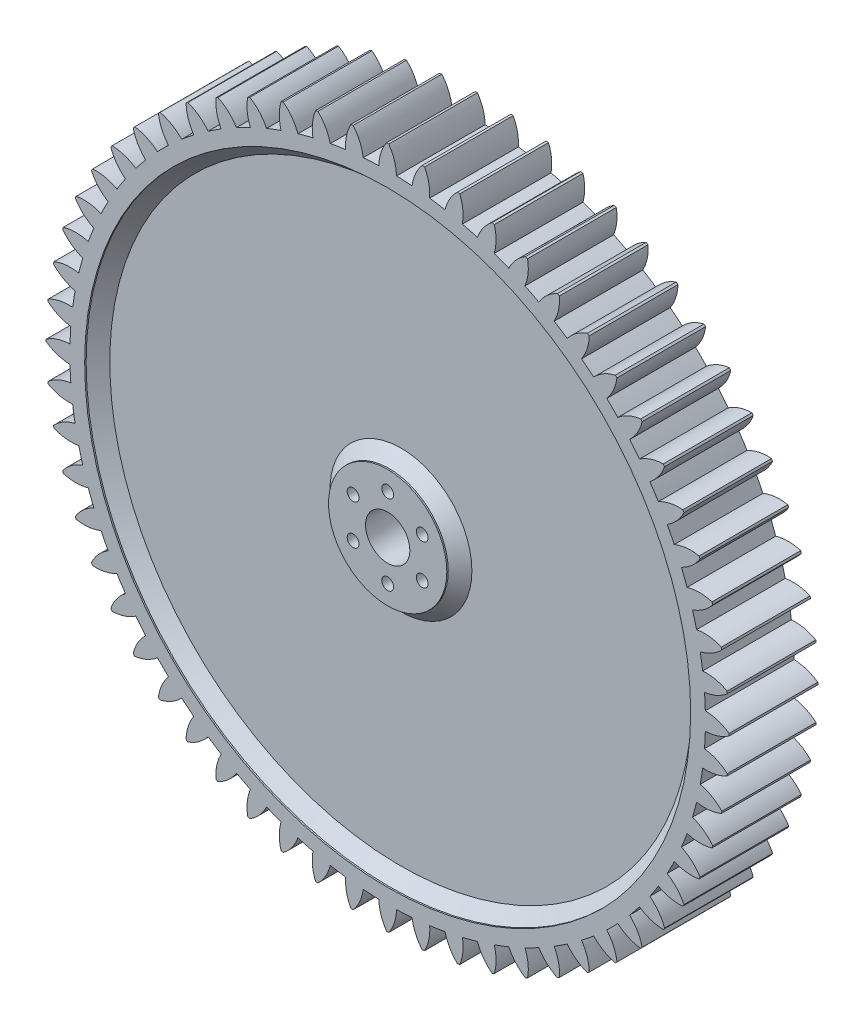
SolidWorks part; units mm, degrees
material "Cast iron, gray, flake graphite, EN GJL 250"
ref_plane "Front Plane" through (0, 0, 0) normal (0, 0, 1) x (1, 0, 0)
ref_plane "Top Plane" through (0, 0, 0) normal (0, 1, 0) x (1, 0, 0)
ref_plane "Right Plane" through (0, 0, 0) normal (1, 0, 0) x (0, 0, -1)
sketch "Sketch8" plane through (0, 0, 0) normal (0, 0, 1) x (1, 0, 0)
  circle A0 centre (0, 0) radius 102.5
  circle A1 centre (0, 0) radius 107.5
  dimension "D1" = 215
  dimension "D2" = 205
extrude "Boss-Extrude1" add sketch "Sketch8" along normal mid plane 30
sketch "Sketch9" plane through (0, 0, 0) normal (0, 0, 1) x (1, 0, 0)
  circle A0 centre (0, 0) radius 20
  dimension "D1" = 40
extrude "Boss-Extrude2" add sketch "Sketch9" along normal mid plane 30 separate body
sketch "Sketch10" plane through (0, 0, 0) normal (0, 0, 1) x (1, 0, 0)
  circle A0 centre (0, 0) radius 20
  circle A1 centre (0, 0) radius 102.5
  circle A2 centre (0, 0) radius 20 construction
  circle A3 centre (0, 0) radius 102.5 construction
extrude "Boss-Extrude3" add sketch "Sketch10" along normal mid plane 21
chamfer "Chamfer2" distance 4 angle 45 4 edges at (102.5, 0, 10.5) (20, 0, 10.5) (102.5, 0, -10.5) (20, 0, -10.5)
sketch "Sketch11" plane through (0, 0, 15) normal (0, 0, 1) x (1, 0, 0)
  circle A0 centre (0, 0) radius 7.5
  dimension "D1" = 15
extrude "Cut-Extrude1" cut sketch "Sketch11" against normal through all
ref_axis "Axis1" through (0, 0, -2.82) along (0, 0, 1)
sketch "Sketch12" plane through (0, 0, 15) normal (0, 0, 1) x (1, 0, 0)
  line L0 (0, 19.5) -> (0, 7.5) construction
  circle A0 centre (0, 0) radius 19.5 construction
  circle A1 centre (0, 0) radius 7.5 construction
  circle A2 centre (0, 13.5) radius 2
  point P10 (0, 13.5)
extrude "Cut-Extrude2" cut sketch "Sketch12" against normal through all
pattern_circular "CirPattern1" count 6 over 360 about axis through (0, 0, -2.82) along (0, 0, 1) of "Cut-Extrude2"
sketch "Sketch13" plane through (0, 0, 15) normal (0, 0, 1) x (1, 0, 0)
  line L0 (-0.375, 115.5) -> (0.375, 115.5)
  line L1 (4.7384, 122.8027) -> (-5.4884, 108.1973) construction
  line L2 (0, 115.5) -> (0, 107.5) construction
  circle A0 centre (0, 0) radius 107.5 construction
  arc A1 (3, 107.4581) -> (-3, 107.4581) centre (0, 0) ccw
  spline S0 degree 2 poles (-3, 107.4581) (-2.8086, 112.0245) (-0.375, 115.5) knots 0 0 0 0.951846 0.951846 0.951846
  spline S1 degree 2 poles (3, 107.4581) (2.8086, 112.0245) (0.375, 115.5) knots 0 0 0 0.951846 0.951846 0.951846
  dimension "D1" = 55
  dimension "D3" = 8
  dimension "D4" = 6
  dimension "D5" = 8.4857
  dimension "D2" = 0.75
extrude "Boss-Extrude4" add sketch "Sketch13" against normal up to surface (30 mm away) up to face at (107.5, 0, -15)
pattern_circular "CirPattern2" count 60 over 360 about axis through (0, 0, 15) along (0, 0, -1) of "Boss-Extrude4"
equation "\"Flywheel Diameter\" = 215mm"
equation "\"Crankshaft Radius\"= 15mm"
equation "\"Flywheel Thickness\" = 30mm"
equation "\"D1@Sketch8\"=\"Flywheel Diameter\""
equation "\"D2@Sketch8\"=\"Flywheel Diameter\"-10mm"
equation "\"D1@Boss-Extrude1\"=\"Flywheel Thickness\""
equation "\"Hub Diameter\" = \"Crankshaft Radius\" + 25mm"
equation "\"D1@Sketch9\"=\"Hub Diameter\""
equation "\"D1@Boss-Extrude2\"=\"Flywheel Thickness\""
equation "\"D1@Boss-Extrude3\"=\"Flywheel Thickness\"*0.7"
equation "\"D1@Sketch11\"=\"Crankshaft Radius\""
equation "\"Bolt Hole Diameter\"= 4mm"
equation "\"D1@Sketch12\"=\"Bolt Hole Diameter\""
